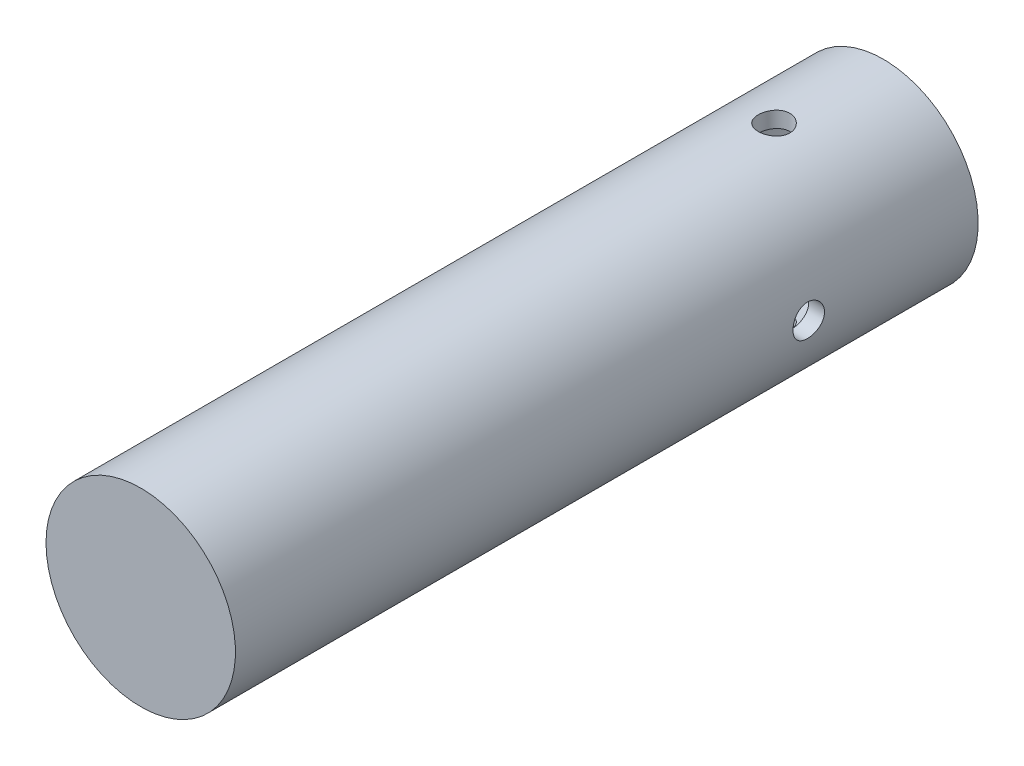
SolidWorks part; units mm, degrees
material "AISI 4130 Steel, annealed at 865C"
ref_plane "X-Y Datum" through (0, 0, 0) normal (0, 0, 1) x (1, 0, 0)
ref_plane "X-Z Datum" through (0, 0, 0) normal (0, 1, 0) x (1, 0, 0)
ref_plane "Y-Z Datum" through (0, 0, 0) normal (1, 0, 0) x (0, 0, -1)
sketch "Sketch9" plane through (0, 0, 0) normal (0, 1, 0) x (1, 0, 0)
  line L0 (16.002, 0) -> (0, 0)
  line L1 (0, 0) -> (0, -389.0916)
  line L2 (0, -389.0916) -> (-72.2493, -524.9728)
  dimension "D1" = 153.895
  dimension "D2" = 28
  dimension "D3" = 389.0916
  dimension "D5" = 16.002
sketch "Sketch5" plane through (0, 0, 0) normal (0, 1, 0) x (1, 0, 0)
  line L0 (7.9375, -96.8417) -> (7.9375, -22.1615)
  line L1 (7.9375, -22.1615) -> (9.525, -22.1615)
  line L2 (9.525, -22.1615) -> (9.525, -96.8417)
  line L3 (9.525, -96.8417) -> (7.9375, -96.8417)
  line L5 (16.002, 0) -> (0, 0) construction
  line L6 (0, 0) -> (0, -389.0916) construction
  line L7 (0, -389.0916) -> (9.525, -389.0916) construction
  line L8 (12.5602, -58.6916) -> (0, -58.6916) construction
  dimension "D1" = 1.5875
  dimension "D2" = 22.1615
  dimension "D3" = 7.9375
  dimension "D4" = 330.4
  dimension "D5" = 292.2499
revolve "Revolve2" add sketch "Sketch5" angle 360 about L1
sketch "Sketch6" plane through (0, 0, 0) normal (0, 1, 0) x (1, 0, 0)
  circle A0 centre (0, -33.1635) radius 1.5875 construction
  circle A1 centre (0, -33.1635) radius 1.5875
sketch "Sketch7" plane through (0, 0, 0) normal (1, 0, 0) x (0, 0, -1)
  circle A2 centre (-39.196, 0) radius 1.5875
  circle A4 centre (-39.196, 0) radius 1.5875 construction
extrude "Cut-Extrude5" cut sketch "Sketch7" against normal through all both and the other way through all
extrude "Cut-Extrude6" cut sketch "Sketch6" against normal through all both and the other way through all
sketch "Sketch8" plane through (0, 0, 0) normal (0, 0, 1) x (1, 0, 0)
  line L0 (9.2357, -0.808) -> (8.6817, -0.254)
  line L1 (8.6817, -0.254) -> (8.6817, 0.254)
  line L2 (8.6817, 0.254) -> (9.2357, 0.808)
  line L3 (8.6817, 0) -> (0, 0) construction
  line L4 (8.9551, -2.3995) -> (8.5057, -1.7577)
  line L5 (8.5057, -1.7577) -> (8.5939, -1.2574)
  line L6 (8.5939, -1.2574) -> (9.2357, -0.808)
  line L7 (8.4024, -3.9181) -> (8.0713, -3.208)
  line L8 (8.0713, -3.208) -> (8.245, -2.7306)
  line L9 (8.245, -2.7306) -> (8.9551, -2.3995)
  line L10 (7.5944, -5.3176) -> (7.3916, -4.5608)
  line L11 (7.3916, -4.5608) -> (7.6456, -4.1209)
  line L12 (7.6456, -4.1209) -> (8.4024, -3.9181)
  line L13 (6.5556, -6.5556) -> (6.4873, -5.7751)
  line L14 (6.4873, -5.7751) -> (6.8138, -5.3859)
  line L15 (6.8138, -5.3859) -> (7.5944, -5.3176)
  line L16 (5.3176, -7.5944) -> (5.3859, -6.8138)
  line L17 (5.3859, -6.8138) -> (5.7751, -6.4873)
  line L18 (5.7751, -6.4873) -> (6.5556, -6.5556)
  line L19 (3.9181, -8.4024) -> (4.1209, -7.6456)
  line L20 (4.1209, -7.6456) -> (4.5608, -7.3916)
  line L21 (4.5608, -7.3916) -> (5.3176, -7.5944)
  line L22 (2.3995, -8.9551) -> (2.7306, -8.245)
  line L23 (2.7306, -8.245) -> (3.208, -8.0713)
  line L24 (3.208, -8.0713) -> (3.9181, -8.4024)
  line L25 (0.808, -9.2357) -> (1.2574, -8.5939)
  line L26 (1.2574, -8.5939) -> (1.7577, -8.5057)
  line L27 (1.7577, -8.5057) -> (2.3995, -8.9551)
  line L28 (-0.808, -9.2357) -> (-0.254, -8.6817)
  line L29 (-0.254, -8.6817) -> (0.254, -8.6817)
  line L30 (0.254, -8.6817) -> (0.808, -9.2357)
  line L31 (-2.3995, -8.9551) -> (-1.7577, -8.5057)
  line L32 (-1.7577, -8.5057) -> (-1.2574, -8.5939)
  line L33 (-1.2574, -8.5939) -> (-0.808, -9.2357)
  line L34 (-3.9181, -8.4024) -> (-3.208, -8.0713)
  line L35 (-3.208, -8.0713) -> (-2.7306, -8.245)
  line L36 (-2.7306, -8.245) -> (-2.3995, -8.9551)
  line L37 (-5.3176, -7.5944) -> (-4.5608, -7.3916)
  line L38 (-4.5608, -7.3916) -> (-4.1209, -7.6456)
  line L39 (-4.1209, -7.6456) -> (-3.9181, -8.4024)
  line L40 (-6.5556, -6.5556) -> (-5.7751, -6.4873)
  line L41 (-5.7751, -6.4873) -> (-5.3859, -6.8138)
  line L42 (-5.3859, -6.8138) -> (-5.3176, -7.5944)
  line L43 (-7.5944, -5.3176) -> (-6.8138, -5.3859)
  line L44 (-6.8138, -5.3859) -> (-6.4873, -5.7751)
  line L45 (-6.4873, -5.7751) -> (-6.5556, -6.5556)
  line L46 (-8.4024, -3.9181) -> (-7.6456, -4.1209)
  line L47 (-7.6456, -4.1209) -> (-7.3916, -4.5608)
  line L48 (-7.3916, -4.5608) -> (-7.5944, -5.3176)
  line L49 (-8.9551, -2.3995) -> (-8.245, -2.7306)
  line L50 (-8.245, -2.7306) -> (-8.0713, -3.208)
  line L51 (-8.0713, -3.208) -> (-8.4024, -3.9181)
  line L52 (-9.2357, -0.808) -> (-8.5939, -1.2574)
  line L53 (-8.5939, -1.2574) -> (-8.5057, -1.7577)
  line L54 (-8.5057, -1.7577) -> (-8.9551, -2.3995)
  line L55 (-9.2357, 0.808) -> (-8.6817, 0.254)
  line L56 (-8.6817, 0.254) -> (-8.6817, -0.254)
  line L57 (-8.6817, -0.254) -> (-9.2357, -0.808)
  line L58 (-8.9551, 2.3995) -> (-8.5057, 1.7577)
  line L59 (-8.5057, 1.7577) -> (-8.5939, 1.2574)
  line L60 (-8.5939, 1.2574) -> (-9.2357, 0.808)
  line L61 (-8.4024, 3.9181) -> (-8.0713, 3.208)
  line L62 (-8.0713, 3.208) -> (-8.245, 2.7306)
  line L63 (-8.245, 2.7306) -> (-8.9551, 2.3995)
  line L64 (-7.5944, 5.3176) -> (-7.3916, 4.5608)
  line L65 (-7.3916, 4.5608) -> (-7.6456, 4.1209)
  line L66 (-7.6456, 4.1209) -> (-8.4024, 3.9181)
  line L67 (-6.5556, 6.5556) -> (-6.4873, 5.7751)
  line L68 (-6.4873, 5.7751) -> (-6.8138, 5.3859)
  line L69 (-6.8138, 5.3859) -> (-7.5944, 5.3176)
  line L70 (-5.3176, 7.5944) -> (-5.3859, 6.8138)
  line L71 (-5.3859, 6.8138) -> (-5.7751, 6.4873)
  line L72 (-5.7751, 6.4873) -> (-6.5556, 6.5556)
  line L73 (-3.9181, 8.4024) -> (-4.1209, 7.6456)
  line L74 (-4.1209, 7.6456) -> (-4.5608, 7.3916)
  line L75 (-4.5608, 7.3916) -> (-5.3176, 7.5944)
  line L76 (-2.3995, 8.9551) -> (-2.7306, 8.245)
  line L77 (-2.7306, 8.245) -> (-3.208, 8.0713)
  line L78 (-3.208, 8.0713) -> (-3.9181, 8.4024)
  line L79 (-0.808, 9.2357) -> (-1.2574, 8.5939)
  line L80 (-1.2574, 8.5939) -> (-1.7577, 8.5057)
  line L81 (-1.7577, 8.5057) -> (-2.3995, 8.9551)
  line L82 (0.808, 9.2357) -> (0.254, 8.6817)
  line L83 (0.254, 8.6817) -> (-0.254, 8.6817)
  line L84 (-0.254, 8.6817) -> (-0.808, 9.2357)
  line L85 (2.3995, 8.9551) -> (1.7577, 8.5057)
  line L86 (1.7577, 8.5057) -> (1.2574, 8.5939)
  line L87 (1.2574, 8.5939) -> (0.808, 9.2357)
  line L88 (3.9181, 8.4024) -> (3.208, 8.0713)
  line L89 (3.208, 8.0713) -> (2.7306, 8.245)
  line L90 (2.7306, 8.245) -> (2.3995, 8.9551)
  line L91 (5.3176, 7.5944) -> (4.5608, 7.3916)
  line L92 (4.5608, 7.3916) -> (4.1209, 7.6456)
  line L93 (4.1209, 7.6456) -> (3.9181, 8.4024)
  line L94 (6.5556, 6.5556) -> (5.7751, 6.4873)
  line L95 (5.7751, 6.4873) -> (5.3859, 6.8138)
  line L96 (5.3859, 6.8138) -> (5.3176, 7.5944)
  line L97 (7.5944, 5.3176) -> (6.8138, 5.3859)
  line L98 (6.8138, 5.3859) -> (6.4873, 5.7751)
  line L99 (6.4873, 5.7751) -> (6.5556, 6.5556)
  line L100 (8.4024, 3.9181) -> (7.6456, 4.1209)
  line L101 (7.6456, 4.1209) -> (7.3916, 4.5608)
  line L102 (7.3916, 4.5608) -> (7.5944, 5.3176)
  line L103 (8.9551, 2.3995) -> (8.245, 2.7306)
  line L104 (8.245, 2.7306) -> (8.0713, 3.208)
  line L105 (8.0713, 3.208) -> (8.4024, 3.9181)
  line L106 (9.2357, 0.808) -> (8.5939, 1.2574)
  line L107 (8.5939, 1.2574) -> (8.5057, 1.7577)
  line L108 (8.5057, 1.7577) -> (8.9551, 2.3995)
  circle A0 centre (0, 0) radius 12.7
  circle A1 centre (0, 0) radius 9.271 construction
  circle A2 centre (0, 0) radius 8.6854 construction
  point P153 (0, 0)
  dimension "D1" = 25.4
  dimension "D4" = 18.542
  dimension "D6" = 17.3708
  dimension "D2" = 0.508
  dimension "D3" = 135
  dimension "D5" = 36
ref_plane "Plane1" through (0, 0, 47.5615) normal (0, 0, -1) x (-1, 0, 0)
sketch "Sketch10" plane through (0, 0, 47.5615) normal (0, 0, -1) x (-1, 0, 0)
  circle A0 centre (0, 0) radius 7.9375
  dimension "D1" = 15.875
extrude "Boss-Extrude1" add sketch "Sketch10" against normal up to surface (49.2802 mm away) up to face at (-9.525, 0, 96.8417)
sketch "Sketch11" plane through (0, 0, 22.1615) normal (0, 0, -1) x (-1, 0, 0)
  line L0 (0, 9.525) -> (13.3548, 9.525) construction
  line L1 (0, 9.525) -> (0, 15.4312) construction
  line L2 (-9.525, 0) -> (-9.525, 9.1744) construction
  line L3 (-9.525, 0) -> (-16.674, 0) construction
  circle A0 centre (0, 0) radius 9.525 construction
  point P0 (0, 9.525)
  point P1 (-9.525, 0)
